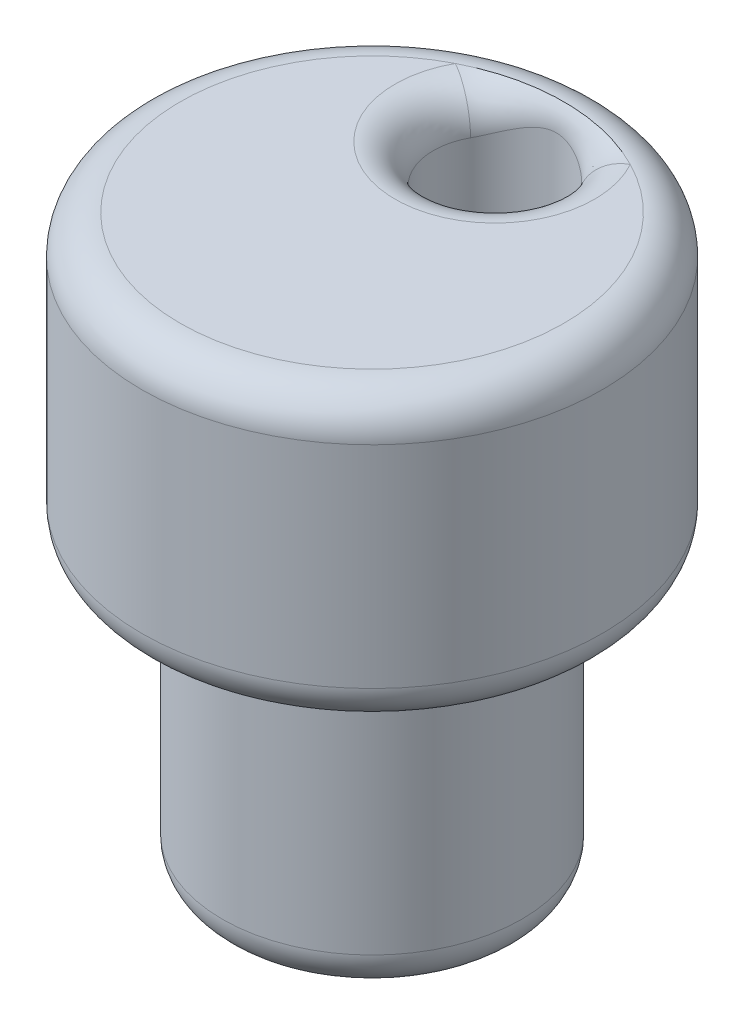
SolidWorks part; units mm, degrees
ref_plane "前视基准面" through (0, 0, 0) normal (0, 0, 1) x (1, 0, 0)
ref_plane "上视基准面" through (0, 0, 0) normal (0, 1, 0) x (1, 0, 0)
ref_plane "右视基准面" through (0, 0, 0) normal (1, 0, 0) x (0, 0, -1)
other "Configuration Table"
sketch "Sketch1" plane through (0, 0, 0) normal (0, 1, 0) x (1, 0, 0)
  circle A0 centre (0, 0) radius 3.9
  dimension "D1" = 7.8
extrude "Boss-Extrude1" add sketch "Sketch1" along normal blind 7.5
sketch "Sketch2" plane through (0, 7.5, 0) normal (0, 1, 0) x (1, 0, 0)
  circle A0 centre (0, 0) radius 6
  circle A1 centre (0, 3.2) radius 1.6
  circle A2 centre (0, 0) radius 3.9 construction
  dimension "D1" = 12
  dimension "D2" = 3.2
  dimension "D3" = 3.2
extrude "Boss-Extrude2" add sketch "Sketch2" along normal blind 7.5
sketch "Sketch3" plane through (0, 7.5, 0) normal (0, 1, 0) x (1, 0, 0)
  circle A0 centre (0, 3.2) radius 1.6 construction
  circle A1 centre (0, 3.2) radius 1.6
extrude "Boss-Extrude3" add sketch "Sketch3" along normal blind 1
fillet "Fillet1" radius 1 3 edges at (0, 0, 3.9) (0, 7.5, 6) (0, 15, 6)
fillet "Fillet2" radius 1 1 edges at (0, 15, -1.6)
